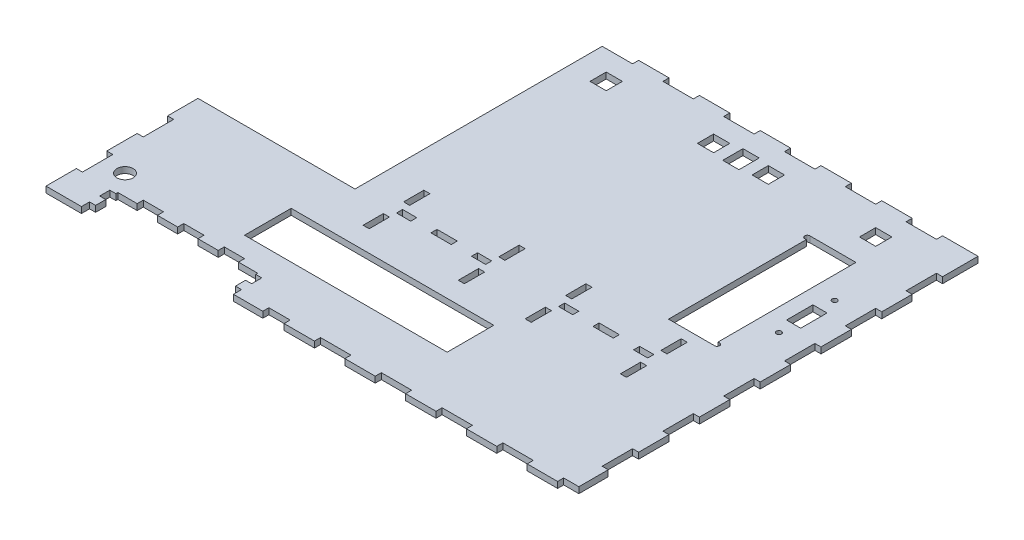
SolidWorks part; units mm, degrees
ref_plane "Alzado" through (0, 0, 0) normal (0, 0, 1) x (1, 0, 0)
ref_plane "Planta" through (0, 0, 0) normal (0, 1, 0) x (1, 0, 0)
ref_plane "Vista lateral" through (0, 0, 0) normal (1, 0, 0) x (0, 0, -1)
sketch "Croquis1" plane through (0, 0, 0) normal (0, 1, 0) x (1, 0, 0)
  line L0 (17.5, 79) -> (20.5, 79)
  line L1 (60, 83) -> (50, 83)
  line L2 (0, 265) -> (17.5, 265) construction
  line L3 (260, 265) -> (260, 247.5)
  line L4 (252.5, 65) -> (237.5, 65)
  line L5 (50, 83) -> (50, 80)
  line L6 (50, 80) -> (40, 80)
  line L7 (40, 80) -> (40, 83)
  line L8 (84.3736, 80) -> (89.5, 80)
  line L9 (40, 83) -> (30, 83)
  line L10 (17.5, 69) -> (20.5, 69)
  line L11 (0, 65) -> (17.5, 65)
  line L12 (92.5, 69) -> (92.5, 65)
  line L13 (20.5, 74) -> (17.5, 74)
  line L14 (92.5, 69) -> (89.5, 69)
  line L15 (30, 83) -> (30, 80)
  line L16 (89.5, 69) -> (89.5, 74)
  line L17 (92.5, 74) -> (92.5, 79)
  line L18 (115, 143) -> (125, 143)
  line L19 (80, 80) -> (84.3736, 80)
  line L20 (89.5, 80) -> (89.5, 79)
  line L21 (30, 80) -> (25.6264, 80)
  line L22 (115, 140) -> (125, 140)
  line L23 (17.5, 69) -> (17.5, 65)
  line L24 (80, 83) -> (80, 80)
  line L25 (89.5, 74) -> (92.5, 74)
  line L26 (70, 83) -> (80, 83)
  line L27 (120, 93) -> (70, 93)
  line L28 (177.5, 65) -> (177.5, 68)
  line L29 (177.5, 68) -> (162.5, 68)
  line L30 (162.5, 68) -> (162.5, 65)
  line L31 (162.5, 65) -> (147.5, 65)
  line L32 (147.5, 65) -> (147.5, 68)
  line L33 (147.5, 68) -> (132.5, 68)
  line L34 (132.5, 68) -> (132.5, 65)
  line L35 (132.5, 65) -> (117.5, 65)
  line L36 (117.5, 65) -> (117.5, 68)
  line L37 (117.5, 68) -> (107, 68)
  line L38 (107, 68) -> (107, 65)
  line L39 (70, 80) -> (70, 83)
  line L40 (92.5, 65) -> (107, 65)
  line L41 (260, 157.5) -> (257, 157.5)
  line L42 (252.5, 68) -> (260, 68)
  line L43 (252.5, 65) -> (252.5, 68)
  line L44 (237.5, 68) -> (237.5, 65)
  line L45 (222.5, 68) -> (237.5, 68)
  line L46 (222.5, 65) -> (222.5, 68)
  line L47 (207.5, 68) -> (207.5, 65)
  line L48 (192.5, 68) -> (207.5, 68)
  line L49 (192.5, 65) -> (192.5, 68)
  line L50 (257, 157.5) -> (257, 142.5)
  line L51 (257, 142.5) -> (260, 142.5)
  line L52 (260, 142.5) -> (260, 127.5)
  line L53 (260, 127.5) -> (257, 127.5)
  line L54 (257, 127.5) -> (257, 112.5)
  line L55 (257, 112.5) -> (260, 112.5)
  line L56 (260, 112.5) -> (260, 97.5)
  line L57 (260, 97.5) -> (257, 97.5)
  line L58 (257, 97.5) -> (257, 82.5)
  line L59 (257, 82.5) -> (260, 82.5)
  line L60 (89.5, 79) -> (92.5, 79)
  line L61 (257, 247.5) -> (260, 247.5)
  line L62 (257, 232.5) -> (257, 247.5)
  line L63 (260, 232.5) -> (257, 232.5)
  line L64 (257, 217.5) -> (260, 217.5)
  line L65 (257, 202.5) -> (257, 217.5)
  line L66 (260, 202.5) -> (257, 202.5)
  line L67 (257, 187.5) -> (260, 187.5)
  line L68 (257, 172.5) -> (257, 187.5)
  line L69 (260, 172.5) -> (257, 172.5)
  line L70 (137.5, 265) -> (137.5, 262)
  line L71 (137.5, 262) -> (152.5, 262)
  line L72 (152.5, 262) -> (152.5, 265)
  line L73 (152.5, 265) -> (167.5, 265)
  line L74 (167.5, 265) -> (167.5, 262)
  line L75 (167.5, 262) -> (182.5, 262)
  line L76 (182.5, 262) -> (182.5, 265)
  line L77 (182.5, 265) -> (197.5, 265)
  line L78 (197.5, 265) -> (197.5, 262)
  line L79 (197.5, 262) -> (212.5, 262)
  line L80 (212.5, 262) -> (212.5, 265)
  line L81 (212.5, 265) -> (227.5, 265)
  line L82 (227.5, 265) -> (227.5, 262)
  line L83 (227.5, 262) -> (242.5, 262)
  line L84 (242.5, 262) -> (242.5, 265)
  line L85 (17.5, 74) -> (17.5, 79)
  line L86 (17.5, 262) -> (17.5, 265) construction
  line L87 (32.5, 262) -> (17.5, 262) construction
  line L88 (32.5, 265) -> (32.5, 262) construction
  line L89 (47.5, 262) -> (47.5, 265) construction
  line L90 (62.5, 262) -> (47.5, 262) construction
  line L91 (62.5, 265) -> (62.5, 262) construction
  line L92 (77.5, 262) -> (77.5, 265) construction
  line L93 (92.5, 262) -> (77.5, 262)
  line L94 (92.5, 265) -> (92.5, 262)
  line L95 (107.5, 262) -> (107.5, 265)
  line L96 (122.5, 262) -> (107.5, 262)
  line L97 (122.5, 265) -> (122.5, 262)
  line L98 (0, 140) -> (3, 140)
  line L99 (3, 140) -> (3, 155) construction
  line L100 (3, 155) -> (0, 155) construction
  line L101 (0, 155) -> (0, 162.5) construction
  line L102 (0, 170) -> (3, 170) construction
  line L103 (3, 170) -> (3, 185) construction
  line L104 (3, 185) -> (0, 185) construction
  line L105 (0, 185) -> (0, 200) construction
  line L106 (0, 200) -> (3, 200) construction
  line L107 (3, 200) -> (3, 215) construction
  line L108 (3, 215) -> (0, 215) construction
  line L109 (0, 215) -> (0, 230) construction
  line L110 (0, 230) -> (3, 230) construction
  line L111 (3, 230) -> (3, 245) construction
  line L112 (3, 245) -> (0, 245) construction
  line L113 (20.5, 69) -> (20.5, 74)
  line L114 (60, 80) -> (70, 80)
  line L115 (60, 83) -> (60, 80)
  line L116 (20.5, 79) -> (20.5, 80)
  line L117 (20.5, 80) -> (25.6264, 80)
  line L118 (70, 93) -> (70, 116)
  line L119 (32.5, 265) -> (47.5, 265) construction
  line L120 (3, 80) -> (0, 80)
  line L121 (3, 95) -> (3, 80)
  line L122 (0, 95) -> (3, 95)
  line L123 (3, 110) -> (0, 110)
  line L124 (3, 125) -> (3, 110)
  line L125 (0, 125) -> (3, 125)
  line L126 (70, 116) -> (170, 116)
  line L127 (170, 116) -> (170, 93)
  line L128 (62.5, 265) -> (77.5, 265) construction
  line L129 (92.5, 265) -> (107.5, 265)
  line L130 (122.5, 265) -> (137.5, 265)
  line L131 (170, 93) -> (120, 93)
  line L132 (195, 143) -> (205, 143)
  line L133 (98, 156.5) -> (98, 146.5)
  line L134 (242.5, 265) -> (260, 265)
  line L135 (0, 245) -> (0, 265) construction
  line L136 (98, 136.5) -> (95, 136.5)
  line L137 (95, 136.5) -> (95, 126.5)
  line L138 (95, 126.5) -> (98, 126.5)
  line L139 (0, 125) -> (0, 140)
  line L140 (0, 95) -> (0, 110)
  line L141 (0, 65) -> (0, 80)
  line L142 (3, 140) -> (77.5, 140)
  line L143 (105, 140) -> (98, 140)
  line L144 (98, 140) -> (98, 143)
  line L145 (98, 143) -> (105, 143)
  line L146 (105, 143) -> (105, 140)
  line L147 (95, 156.5) -> (98, 156.5)
  line L148 (95, 146.5) -> (95, 156.5)
  line L149 (98, 146.5) -> (95, 146.5)
  line L150 (192.5, 65) -> (177.5, 65)
  line L151 (222.5, 65) -> (207.5, 65)
  line L152 (260, 82.5) -> (260, 68)
  line L153 (142, 146.5) -> (145, 146.5)
  line L154 (145, 146.5) -> (145, 156.5)
  line L155 (260, 172.5) -> (260, 157.5)
  line L156 (260, 202.5) -> (260, 187.5)
  line L157 (260, 232.5) -> (260, 217.5)
  line L158 (145, 156.5) -> (142, 156.5)
  line L159 (98, 126.5) -> (98, 136.5)
  line L160 (77.5, 140) -> (77.5, 155)
  line L161 (142, 156.5) -> (142, 146.5)
  line L162 (142, 126.5) -> (142, 136.5)
  line L163 (145, 126.5) -> (142, 126.5)
  line L164 (145, 136.5) -> (145, 126.5)
  line L165 (142, 136.5) -> (145, 136.5)
  line L166 (178, 156.5) -> (178, 146.5)
  line L167 (175, 156.5) -> (178, 156.5)
  line L168 (135, 143) -> (135, 140)
  line L169 (142, 143) -> (135, 143)
  line L170 (142, 140) -> (142, 143)
  line L171 (135, 140) -> (142, 140)
  line L172 (125, 143) -> (125, 140)
  line L173 (115, 140) -> (115, 143)
  line L174 (185, 140) -> (178, 140)
  line L175 (175, 146.5) -> (175, 156.5)
  line L176 (178, 140) -> (178, 143)
  line L177 (178, 146.5) -> (175, 146.5)
  line L178 (222, 146.5) -> (225, 146.5)
  line L179 (225, 146.5) -> (225, 156.5)
  line L180 (222, 140) -> (222, 143)
  line L181 (225, 156.5) -> (222, 156.5)
  line L182 (222, 156.5) -> (222, 146.5)
  line L183 (178, 136.5) -> (175, 136.5)
  line L184 (175, 136.5) -> (175, 126.5)
  line L185 (178, 143) -> (185, 143)
  line L186 (175, 126.5) -> (178, 126.5)
  line L187 (205, 140) -> (205, 143)
  line L188 (185, 143) -> (185, 140)
  line L189 (178, 126.5) -> (178, 136.5)
  line L190 (222, 126.5) -> (222, 136.5)
  line L191 (225, 126.5) -> (222, 126.5)
  line L192 (225, 136.5) -> (225, 126.5)
  line L193 (222, 136.5) -> (225, 136.5)
  line L194 (0, 170) -> (0, 162.5) construction
  line L195 (215, 143) -> (215, 140)
  line L196 (77.5, 155) -> (77.5, 262)
  line L197 (93.5, 248) -> (93.5, 244) construction
  line L198 (89.5, 252) -> (97.5, 252)
  line L199 (215, 140) -> (222, 140)
  line L200 (195, 140) -> (205, 140)
  line L201 (89.5, 252) -> (89.5, 244)
  line L202 (89.5, 244) -> (97.5, 244)
  line L203 (97.5, 252) -> (97.5, 244)
  line L204 (222, 143) -> (215, 143)
  line L205 (195, 140) -> (195, 143)
  line L206 (89.5, 252) -> (97.5, 244) construction
  line L207 (89.5, 244) -> (97.5, 252) construction
  line L208 (146.5, 248) -> (146.5, 244) construction
  line L209 (142.5, 252) -> (150.5, 252)
  line L210 (142.5, 252) -> (142.5, 244)
  line L211 (142.5, 244) -> (150.5, 244)
  line L212 (150.5, 252) -> (150.5, 244)
  line L213 (142.5, 252) -> (150.5, 244) construction
  line L214 (142.5, 244) -> (150.5, 252) construction
  line L215 (173.5, 248) -> (173.5, 244) construction
  line L216 (169.5, 252) -> (177.5, 252)
  line L217 (169.5, 252) -> (169.5, 244)
  line L218 (169.5, 244) -> (177.5, 244)
  line L219 (177.5, 252) -> (177.5, 244)
  line L220 (169.5, 252) -> (177.5, 244) construction
  line L221 (169.5, 244) -> (177.5, 252) construction
  line L222 (226.5, 248) -> (226.5, 244) construction
  line L223 (222.5, 252) -> (230.5, 252)
  line L224 (222.5, 252) -> (222.5, 244)
  line L225 (222.5, 244) -> (230.5, 244)
  line L226 (230.5, 252) -> (230.5, 244)
  line L227 (222.5, 252) -> (230.5, 244) construction
  line L228 (222.5, 244) -> (230.5, 252) construction
  dimension "D6" = 10
  dimension "D14" = 8
  dimension "D16" = 3
  dimension "D70" = 8
  dimension "D7" = 50
  dimension "D8" = 10
  dimension "D9" = 10
  dimension "D10" = 23
  dimension "D11" = 100
  dimension "D12" = 16
  dimension "D13" = 10
  dimension "D15" = 14
  dimension "D17" = 15
  dimension "D18" = 3
  dimension "D19" = 15
  dimension "D20" = 15
  dimension "D21" = 14.5
  dimension "D22" = 15
  dimension "D23" = 74.5
  dimension "D24" = 15
  dimension "D25" = 3
  dimension "D26" = 15
  dimension "D27" = 15
  dimension "D28" = 15
  dimension "D29" = 15
  dimension "D30" = 15
  dimension "D31" = 15
  dimension "D32" = 15
  dimension "D33" = 15
  dimension "D34" = 3
  dimension "D35" = 15
  dimension "D36" = 15
  dimension "D37" = 15
  dimension "D38" = 15
  dimension "D39" = 15
  dimension "D40" = 15
  dimension "D41" = 15
  dimension "D42" = 15
  dimension "D43" = 3
  dimension "D44" = 3
  dimension "D45" = 17.5
  dimension "D46" = 17.5
  dimension "D47" = 15
  dimension "D48" = 3
  dimension "D49" = 15
  dimension "D50" = 15
  dimension "D51" = 15
  dimension "D52" = 3
  dimension "D53" = 15
  dimension "D54" = 15
  dimension "D55" = 15
  dimension "D56" = 15
  dimension "D57" = 15
  dimension "D58" = 3
  dimension "D59" = 17.5
  dimension "D60" = 4
  dimension "D61" = 10
  dimension "D62" = 65
  dimension "D63" = 8
  dimension "D64" = 8
  dimension "D65" = 15
  dimension "D66" = 107
  dimension "D67" = 3
  dimension "D68" = 14
  dimension "D69" = 69
  dimension "D71" = 3
  dimension "D72" = 8
  dimension "D73" = 8
  dimension "D74" = 27
  dimension "D75" = 53
  dimension "D76" = 8
  dimension "D77" = 8
extrude "Saliente-Extruir1" add sketch "Croquis1" along normal blind 3
sketch "Sketch1" plane through (0, 0, 0) normal (0, -1, 0) x (1, 0, 0)
  line L0 (247, -190.5) -> (247, -203.5)
  line L1 (247, -203.5) -> (240, -203.5)
  line L2 (240, -203.5) -> (240, -190.5)
  line L3 (240, -190.5) -> (247, -190.5)
  line L4 (260, -187.5) -> (260, -202.5) construction
  line L5 (260, -265) -> (242.5, -265) construction
  line L6 (210.5, -161.75) -> (232.5, -161.75)
  line L7 (210.5, -161.75) -> (210.5, -229.75)
  line L8 (211, -232.25) -> (232.5, -232.25)
  line L9 (243.5, -182) -> (243.5, -212) construction
  line L10 (210.5, -161.75) -> (232.5, -232.25) construction
  line L11 (211, -232.25) -> (231.7344, -163) construction
  line L13 (221.5, -197) -> (229.5, -197) construction
  line L14 (240, -197) -> (247, -197) construction
  line L15 (233.25, -163) -> (209.75, -163) construction
  line L16 (209.75, -163) -> (209.75, -231) construction
  line L17 (221.5, -163) -> (221.5, -232.25) construction
  line L18 (221.5, -161.75) -> (221.5, -197) construction
  line L19 (211, -232.25) -> (209.75, -232.25)
  line L20 (209.75, -229.75) -> (210.5, -229.75)
  line L21 (233.25, -161.75) -> (232.5, -161.75)
  line L22 (233.25, -164.25) -> (232.5, -164.25)
  line L23 (232.5, -164.25) -> (232.5, -232.25)
  arc A0 (209.75, -229.75) -> (209.75, -232.25) centre (209.75, -231) ccw
  arc A1 (233.25, -164.25) -> (233.25, -161.75) centre (233.25, -163) ccw
  circle A2 centre (243.5, -210.75) radius 1.25
  circle A3 centre (243.5, -183.25) radius 1.25
  point P4 (260, -195)
  point P7 (221.5277, -197.0889)
  point P14 (251.25, -265)
  point P37 (243.5, -197)
  dimension "D8" = 2.5
  dimension "D9" = 2.5
  dimension "D12" = 2.5
  dimension "D1" = 13
  dimension "D2" = 13
  dimension "D3" = 7
  dimension "D4" = 11.75
  dimension "D5" = 15
  dimension "D6" = 70.5
  dimension "D7" = 68
  dimension "D10" = 1.25
  dimension "D11" = 1.25
  dimension "D13" = 22
  dimension "D14" = 14.5
extrude "Cut-Extrude2" cut sketch "Sketch1" against normal blind 10
sketch "Sketch2" plane through (0, 3, 0) normal (0, 1, 0) x (1, 0, 0)
  line L0 (169.5, 248) -> (150.5, 248) construction
  line L1 (169.5, 252) -> (169.5, 244) construction
  line L2 (150.5, 244) -> (150.5, 252) construction
  line L4 (164, 243) -> (156, 243)
  line L5 (164, 243) -> (164, 253)
  line L6 (164, 253) -> (156, 253)
  line L7 (156, 243) -> (156, 253)
  line L8 (164, 243) -> (156, 253) construction
  line L9 (164, 253) -> (156, 243) construction
  point P6 (160, 248)
  dimension "D1" = 8
  dimension "D2" = 10
extrude "Cut-Extrude3" cut sketch "Sketch2" against normal blind 10
sketch "Sketch3" plane through (0, 3, 0) normal (0, 1, 0) x (1, 0, 0)
  line L0 (20.5, 80) -> (30, 80) construction
  circle A0 centre (14, 90) radius 4
  point P2 (25.25, 80)
  dimension "D1" = 8
  dimension "D2" = 14
  dimension "D3" = 10
extrude "Cut-Extrude4" cut sketch "Sketch3" against normal blind 10
